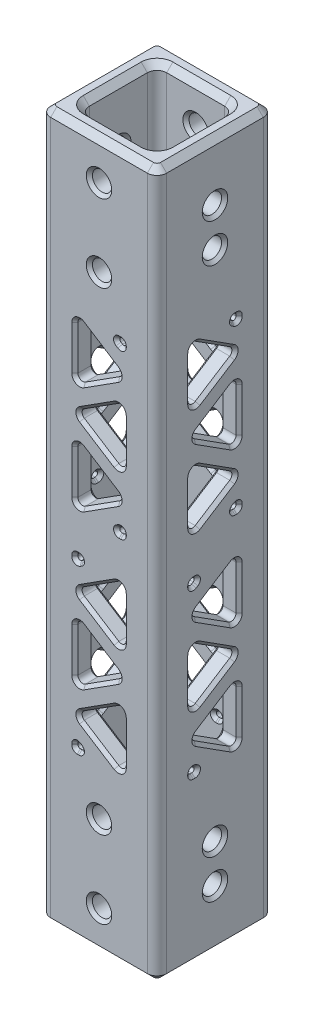
SolidWorks part; units mm, degrees
note: '?' marks a value the reader was unsure of.
ref_plane "Front Plane" through (0, 0, 0) normal (0, 0, 1) x (1, 0, 0)
ref_plane "Top Plane" through (0, 0, 0) normal (0, 1, 0) x (1, 0, 0)
ref_plane "Right Plane" through (0, 0, 0) normal (1, 0, 0) x (0, 0, -1)
sketch "Sketch1" plane through (0, 0, 0) normal (0, 1, 0) x (1, 0, 0)
  line L1 (-9.525, -9.525) -> (9.525, -9.525)
  line L2 (-9.525, -9.525) -> (-9.525, 9.525)
  line L3 (-9.525, 9.525) -> (9.525, 9.525)
  line L4 (9.525, -9.525) -> (9.525, 9.525)
  line L5 (-9.525, -9.525) -> (9.525, 9.525) construction
  line L6 (-9.525, 9.525) -> (9.525, -9.525) construction
  line L7 (-6.35, -6.35) -> (6.35, -6.35)
  line L8 (-6.35, -6.35) -> (-6.35, 6.35)
  line L9 (-6.35, 6.35) -> (6.35, 6.35)
  line L10 (6.35, -6.35) -> (6.35, 6.35)
  line L11 (-6.35, -6.35) -> (6.35, 6.35) construction
  line L12 (-6.35, 6.35) -> (6.35, -6.35) construction
  point P0 (0, 0)
  point P6 (0, 0)
  dimension "D1" = 19.05
  dimension "D2" = 19.05
  dimension "D3" = 12.7
extrude "Boss-Extrude1" add sketch "Sketch1" along normal mid plane 115.8875 contours L3 L4 L1 L2
hole_wizard "1/8 (0.125) Diameter Hole1" positions "Sketch15" profile "Sketch16" hole size "1/8" standard "ANSI Inch" end condition through all
sketch "Sketch15" plane through (0, 0, 9.525) normal (0, 0, -1) x (-1, 0, 0)
  line L0 (0, 38.8937) -> (0, 51.5937) construction
  line L4 (9.525, 57.9437) -> (-9.525, 57.9437) construction
  line L8 (0, 51.5937) -> (0, 57.9437) construction
  line L9 (0, -57.9437) -> (0, -51.5937) construction
  line L10 (-9.525, -57.9437) -> (9.525, -57.9437) construction
  line L11 (0, -51.5937) -> (0, -38.8937) construction
  point P0 (0, 51.5937)
  point P2 (0, 38.8937)
  point P4 (0, -38.8937)
  point P6 (0, -51.5937)
  dimension "D1" = 12.7
  dimension "D2" = 6.35
sketch "Sketch16" plane through (0, 51.5937, 9.525) normal (1, 0, 0) x (0, -1, 0)
  line L0 (0, 0) -> (0, 19.05)
  line L1 (0, 19.05) -> (1.5875, 19.05)
  line L2 (1.5875, 19.05) -> (1.5875, 0)
  line L5 (1.5875, 0) -> (0, 0)
  line L11 (0, -6.35) -> (0, 107.95) construction
  dimension "Thru Hole Dia." = 3.175
  dimension "Thru Hole Depth" = 19.05
hole_wizard "1/8 (0.125) Diameter Hole2" positions "Sketch8" profile "Sketch9" hole size "1/8" standard "ANSI Inch" end condition through all
sketch "Sketch8" plane through (-9.525, 0, 0) normal (-1, 0, 0) x (0, 0, 1)
  line L2 (0, 48.4187) -> (0, 57.9437) construction
  line L3 (-9.525, 57.9437) -> (9.525, 57.9437) construction
  point P0 (0, 48.4187)
  point P2 (0, 42.0687)
  dimension "D1" = 6.35
  dimension "D2" = 9.525
sketch "Sketch9" plane through (-9.525, 48.4187, 0) normal (0, 1, 0) x (0, 0, 1)
  line L0 (0, 0) -> (0, 19.05)
  line L1 (0, 19.05) -> (1.5875, 19.05)
  line L2 (1.5875, 19.05) -> (1.5875, 0)
  line L5 (1.5875, 0) -> (0, 0)
  line L11 (0, -6.35) -> (0, 107.95) construction
  dimension "Thru Hole Dia." = 3.175
  dimension "Thru Hole Depth" = 19.05
hole_wizard "1/8 (0.125) Diameter Hole3" positions "Sketch10" profile "Sketch11" hole size "1/8" standard "ANSI Inch" end condition through all
sketch "Sketch10" plane through (9.525, 0, 0) normal (1, 0, 0) x (0, 0, -1)
  line L0 (0, -57.9437) -> (0, -48.4187) construction
  line L1 (-9.525, -57.9437) -> (9.525, -57.9437) construction
  point P0 (0, -42.0687)
  point P2 (0, -48.4187)
  dimension "D1" = 6.35
  dimension "D2" = 9.525
sketch "Sketch11" plane through (9.525, -42.0687, 0) normal (0, 1, 0) x (0, 0, -1)
  line L0 (0, 0) -> (0, 19.05)
  line L1 (0, 19.05) -> (1.5875, 19.05)
  line L2 (1.5875, 19.05) -> (1.5875, 0)
  line L5 (1.5875, 0) -> (0, 0)
  line L11 (0, -6.35) -> (0, 107.95) construction
  dimension "Thru Hole Dia." = 3.175
  dimension "Thru Hole Depth" = 19.05
sketch "Sketch14" plane through (0, 0, 0) normal (0, 0, 1) x (1, 0, 0)
  line L0 (-3.9688, 30.9562) -> (3.9688, 30.9562) construction
  line L3 (3.9688, 30.9562) -> (3.9688, -30.9562) construction
  line L4 (3.9688, -30.9562) -> (-3.9688, -30.9562) construction
  line L5 (-3.9688, -30.9562) -> (-3.9688, 30.9562) construction
  line L6 (-3.9688, 30.9562) -> (-1.9357, 30.9562)
  line L7 (-1.9357, 30.9562) -> (-3.9688, 29.6596)
  line L8 (0, 30.9562) -> (0, 37.3062) construction
  line L11 (0, -37.3062) -> (0, -30.9562) construction
  line L12 (-3.9688, 3.175) -> (3.9688, 3.175) construction
  line L13 (-3.9688, -3.175) -> (3.9688, -3.175) construction
  line L14 (0, -3.175) -> (0, 3.175) construction
  line L15 (0, -30.9562) -> (0, -3.175) construction
  line L16 (0, 3.175) -> (0, 30.9562) construction
  line L17 (-3.9688, 29.6596) -> (-3.9688, 30.9562)
  line L18 (3.9688, 30.9562) -> (-3.9688, 25.8938)
  line L19 (-3.9688, 25.8938) -> (3.9688, 20.8314)
  line L20 (3.9688, 20.8314) -> (3.9688, 30.9562)
  line L21 (0, 28.425) -> (-1.7073, 31.1019) construction
  line L22 (-3.9688, 22.128) -> (3.9688, 17.0656)
  line L23 (3.9688, 17.0656) -> (-3.9688, 12.0032)
  line L24 (-3.9688, 12.0032) -> (-3.9688, 22.128)
  line L25 (0, 23.3626) -> (-1.7073, 20.6857) construction
  line L26 (3.9688, 13.2998) -> (-3.9688, 8.2374)
  line L27 (-3.9688, 8.2374) -> (3.9688, 3.175)
  line L28 (3.9688, 3.175) -> (3.9688, 13.2998)
  line L29 (0, 14.5344) -> (1.7073, 11.8575) construction
  line L30 (-1.9357, 3.175) -> (-3.9688, 3.175)
  line L31 (-3.9688, 3.175) -> (-3.9688, 4.4716)
  line L32 (-3.9688, 4.4716) -> (-1.9357, 3.175)
  line L33 (-2.9522, 3.8233) -> (-1.2449, 6.5002) construction
  line L34 (1.9357, -3.175) -> (3.9688, -3.175)
  line L35 (3.9688, -3.175) -> (3.9688, -4.4716)
  line L36 (3.9688, -4.4716) -> (1.9357, -3.175)
  line L37 (-3.9688, -3.175) -> (3.9688, -8.2374)
  line L38 (3.9688, -8.2374) -> (-3.9688, -13.2998)
  line L39 (-3.9688, -13.2998) -> (-3.9688, -3.175)
  line L40 (2.9522, -3.8233) -> (1.2449, -6.5002) construction
  line L41 (3.9688, -12.0032) -> (-3.9688, -17.0656)
  line L42 (-3.9688, -17.0656) -> (3.9688, -22.128)
  line L43 (3.9688, -22.128) -> (3.9688, -12.0032)
  line L44 (0, -14.5344) -> (-1.7073, -11.8575) construction
  line L45 (-3.9688, -30.9562) -> (3.9688, -25.8938)
  line L46 (3.9688, -25.8938) -> (-3.9688, -20.8314)
  line L47 (-3.9688, -20.8314) -> (-3.9688, -30.9562)
  line L48 (0, -23.3626) -> (1.7073, -20.6857) construction
  line L49 (1.9357, -30.9562) -> (3.9688, -30.9562)
  line L50 (3.9688, -30.9562) -> (3.9688, -29.6596)
  line L51 (3.9688, -29.6596) -> (1.9357, -30.9562)
  line L52 (2.9522, -30.3079) -> (1.2449, -27.631) construction
  line L54 (9.525, 57.9437) -> (9.525, -57.9437) construction
  circle A2 centre (0, -38.8937) radius 1.5875 construction
  circle A3 centre (0, 38.8937) radius 1.5875 construction
  dimension "D3" = 3.175
  dimension "D1" = 7.9375
  dimension "D2" = 6.35
extrude "Cut-Extrude1" cut sketch "Sketch14" against normal through all
ref_axis "Axis1" through (0, 63.7381, 0) along (0, -1, 0)?
pattern_circular "CirPattern2" count 4 over 360 about axis through (0, 0, 0) along (0, 1, 0) of "Cut-Extrude1"
fillet "Fillet1" radius 1.5875 8 edges at (9.525, 0, -9.525) (9.525, 0, 9.525) (-9.525, 0, -9.525) (-9.525, 0, 9.525) (6.35, 0, -6.35) (6.35, 0, 6.35) (-6.35, 0, 6.35) (-6.35, 0, -6.35)
fillet "Fillet2" radius 0.7937 72 edges at (3.9688, 30.9562, -7.9375) (3.9688, 20.8314, -7.9375) (-3.9687, 25.8938, -7.9375) (-3.9688, 12.0032, -7.9375) (-3.9688, 22.128, -7.9375) (3.9688, 17.0656, -7.9375) (-3.9688, -13.2998, -7.9375) (-3.9688, -3.175, -7.9375) (3.9688, -8.2374, -7.9375) (3.9688, 13.2998, -7.9375) (3.9688, 3.175, -7.9375) (-3.9687, 8.2374, -7.9375) (-3.9688, -30.9562, -7.9375) (-3.9688, -20.8314, -7.9375) (3.9688, -25.8938, -7.9375) (3.9688, -12.0032, -7.9375) (3.9688, -22.128, -7.9375) (-3.9688, -17.0656, -7.9375) (7.9375, -12.0032, 3.9688) (-7.9375, -13.2998, 3.9687) (7.9375, -13.2998, -3.9687) (7.9375, -30.9563, -3.9687) (-7.9375, -12.0032, -3.9688) (-7.9375, -30.9563, 3.9687) (7.9375, -22.128, 3.9688) (7.9375, -17.0656, -3.9687) (3.9688, -30.9562, 7.9375) (3.9688, -20.8314, 7.9375) (-3.9688, -25.8938, 7.9375) (3.9688, -13.2998, 7.9375) (3.9688, -3.175, 7.9375) (-3.9688, -8.2374, 7.9375) (7.9375, -20.8314, -3.9687) (7.9375, -25.8938, 3.9688) (7.9375, -3.175, -3.9687) (7.9375, -8.2374, 3.9688) (-3.9688, -12.0032, 7.9375) (-3.9688, -22.128, 7.9375) (3.9688, -17.0656, 7.9375) (-7.9375, -20.8314, 3.9687) (-7.9375, -25.8938, -3.9688) (-7.9375, -22.128, -3.9688) (-7.9375, -17.0656, 3.9687) (-7.9375, -3.175, 3.9687) (-7.9375, -8.2374, -3.9688) (7.9375, 12.0032, -3.9687) (-7.9375, 13.2998, -3.9688) (7.9375, 13.2998, 3.9688) (7.9375, 30.9562, 3.9688) (-7.9375, 30.9563, -3.9688) (-7.9375, 12.0032, 3.9687) (7.9375, 3.175, 3.9688) (7.9375, 8.2374, -3.9687) (-3.9688, 13.2998, 7.9375) (-3.9688, 3.175, 7.9375) (3.9687, 8.2374, 7.9375) (-3.9688, 30.9562, 7.9375) (-3.9688, 20.8314, 7.9375) (3.9688, 25.8938, 7.9375) (-7.9375, 20.8314, -3.9688) (-7.9375, 25.8938, 3.9687) (-7.9375, 22.128, 3.9687) (-7.9375, 17.0656, -3.9688) (3.9688, 12.0032, 7.9375) (3.9688, 22.128, 7.9375) (-3.9688, 17.0656, 7.9375) (7.9375, 20.8314, 3.9688) (7.9375, 25.8938, -3.9687) (7.9375, 22.128, -3.9687) (7.9375, 17.0656, 3.9688) (-7.9375, 3.175, -3.9688) (-7.9375, 8.2374, 3.9687)
fillet "Fillet3" radius 0.3969 48 edges at (3.9688, -3.175, -7.9375) (3.9688, -4.4716, -7.9375) (1.9357, -3.175, -7.9375) (-3.9688, 3.175, -7.9375) (-3.9688, 4.4716, -7.9375) (-1.9357, 3.175, -7.9375) (3.9688, -29.6596, -7.9375) (3.9688, -30.9562, -7.9375) (1.9357, -30.9563, -7.9375) (-3.9687, 29.6596, -7.9375) (-3.9688, 30.9562, -7.9375) (-1.9357, 30.9562, -7.9375) (-7.9375, -29.6596, -3.9688) (7.9375, -29.6596, 3.9688) (7.9375, -30.9562, 1.9357) (7.9375, -30.9562, 3.9688) (-7.9375, -3.175, -3.9688) (7.9375, -3.175, 3.9688) (7.9375, -4.4716, 3.9688) (7.9375, -3.175, 1.9357) (-7.9375, -4.4716, -3.9688) (-7.9375, -3.175, -1.9357) (-7.9375, -30.9562, -3.9688) (-7.9375, -30.9563, -1.9357) (-3.9688, -3.175, 7.9375) (-3.9688, -4.4716, 7.9375) (-1.9357, -3.175, 7.9375) (-3.9688, -29.6596, 7.9375) (-1.9357, -30.9562, 7.9375) (-3.9688, -30.9562, 7.9375) (7.9375, 29.6596, -3.9687) (7.9375, 3.175, -3.9687) (7.9375, 30.9562, -3.9687) (7.9375, 30.9562, -1.9357) (3.9688, 3.175, 7.9375) (3.9688, 4.4716, 7.9375) (1.9357, 3.175, 7.9375) (-7.9375, 29.6596, 3.9687) (-7.9375, 30.9562, 3.9687) (-7.9375, 30.9562, 1.9357) (3.9688, 29.6596, 7.9375) (3.9688, 30.9562, 7.9375) (1.9357, 30.9562, 7.9375) (-7.9375, 3.175, 3.9687) (-7.9375, 4.4716, 3.9687) (-7.9375, 3.175, 1.9357) (7.9375, 4.4716, -3.9687) (7.9375, 3.175, -1.9357)
chamfer "Chamfer1" distance 1.016 angle 45 32 edges at (9.525, 57.9437, 0) (9.06, 57.9437, -9.06) (9.06, 57.9437, 9.06) (0, 57.9437, -9.525) (0, 57.9437, 9.525) (-9.06, 57.9437, -9.06) (-9.06, 57.9437, 9.06) (-9.525, 57.9437, 0) (6.35, 57.9437, 0) (5.885, 57.9437, -5.885) (5.885, 57.9437, 5.885) (0, 57.9437, -6.35) (0, 57.9437, 6.35) (-5.885, 57.9437, -5.885) (-5.885, 57.9437, 5.885) (-6.35, 57.9437, 0) (0, -57.9437, 9.525) (9.06, -57.9437, 9.06) (-9.06, -57.9437, 9.06) (9.525, -57.9437, 0) (-9.525, -57.9437, 0) (9.06, -57.9437, -9.06) (-9.06, -57.9437, -9.06) (0, -57.9437, -9.525) (0, -57.9437, 6.35) (5.885, -57.9437, 5.885) (-5.885, -57.9437, 5.885) (6.35, -57.9437, 0) (-6.35, -57.9437, 0) (5.885, -57.9437, -5.885) (-5.885, -57.9437, -5.885) (0, -57.9437, -6.35)
chamfer "Chamfer2" distance 0.508 angle 45 512 edges at (9.525, -12.5482, -3.5566) (6.35, 21.3764, -3.5566) (9.525, 21.3764, -3.5566) (6.35, 17.0656, 3.2864) (9.525, 17.0656, 3.2864) (6.35, 12.7549, -3.5566) (9.525, 12.7549, -3.5566) (6.35, 21.5831, 3.5566) (9.525, 21.5831, 3.5566) (6.35, 30.2046, 3.5566) (9.525, 30.2046, 3.5566) (6.35, 25.8938, -3.2864) (9.525, 25.8938, -3.2864) (3.5566, -21.3764, -6.35) (3.5566, -21.3764, -9.525) (-3.2864, -17.0656, -6.35) (-3.2864, -17.0656, -9.525) (3.5566, -12.7549, -6.35) (3.5566, -12.7549, -9.525) (-3.5566, -21.5831, -6.35) (-3.5566, -21.5831, -9.525) (3.2864, -25.8938, -6.35) (3.2864, -25.8938, -9.525) (-3.5566, -30.2046, -6.35) (-3.5566, -30.2046, -9.525) (3.5566, 3.9267, -6.35) (3.5566, 3.9267, -9.525) (-3.2864, 8.2374, -6.35) (-3.2864, 8.2374, -9.525) (3.5566, 12.5482, -6.35) (3.5566, 12.5482, -9.525) (-3.5566, -3.9267, -6.35) (-3.5566, -3.9267, -9.525) (3.2864, -8.2374, -6.35) (3.2864, -8.2374, -9.525) (-3.5566, -12.5482, -6.35) (-3.5566, -12.5482, -9.525) (-3.5566, 21.3764, -6.35) (-3.5566, 21.3764, -9.525) (3.2864, 17.0656, -6.35) (3.2864, 17.0656, -9.525) (-3.5566, 12.7549, -6.35) (-3.5566, 12.7549, -9.525) (3.5566, 21.5831, -6.35) (3.5566, 21.5831, -9.525) (3.5566, 30.2046, -6.35) (3.5566, 30.2046, -9.525) (-3.2864, 25.8938, -6.35) (-3.2864, 25.8938, -9.525) (-3.434, -30.9562, 6.35) (-3.434, -30.9562, 9.525) (-3.2206, -30.1368, 6.35) (-3.2206, -30.1368, 9.525) (-3.9688, -30.4714, 6.35) (-3.9688, -30.4714, 9.525) (-3.2206, -3.9944, 6.35) (-3.2206, -3.9944, 9.525) (-3.434, -3.175, 6.35) (-3.434, -3.175, 9.525) (-3.9688, -3.6598, 6.35) (-3.9688, -3.6598, 9.525) (3.2206, 3.9944, 6.35) (3.2206, 3.9944, 9.525) (3.434, 3.175, 6.35) (3.434, 3.175, 9.525) (3.9688, 3.6598, 6.35) (3.9688, 3.6598, 9.525) (3.2206, 30.1368, 6.35) (3.2206, 30.1368, 9.525) (3.9688, 30.4714, 6.35) (3.9688, 30.4714, 9.525) (3.434, 30.9562, 6.35) (3.434, 30.9562, 9.525) (-6.35, -30.9562, -3.434) (-9.525, -30.9562, -3.434) (-6.35, -30.1368, -3.2206) (-9.525, -30.1368, -3.2206) (-6.35, -30.4714, -3.9688) (-9.525, -30.4714, -3.9688) (-6.35, -3.9944, -3.2206) (-9.525, -3.9944, -3.2206) (-6.35, -3.175, -3.434) (-9.525, -3.175, -3.434) (-6.35, -3.6598, -3.9688) (-9.525, -3.6598, -3.9688) (-6.35, 3.175, 3.434) (-9.525, 3.175, 3.434) (-6.35, 3.6598, 3.9687) (-9.525, 3.6598, 3.9687) (-6.35, 3.9944, 3.2206) (-9.525, 3.9944, 3.2206) (-6.35, 30.9562, 3.434) (-9.525, 30.9562, 3.434) (-6.35, 30.1368, 3.2206) (-9.525, 30.1368, 3.2206) (-6.35, 30.4714, 3.9687) (-9.525, 30.4714, 3.9687) (6.35, 30.9562, -3.434) (9.525, 30.9562, -3.434) (6.35, 30.1368, -3.2206) (9.525, 30.1368, -3.2206) (6.35, 30.4714, -3.9687) (9.525, 30.4714, -3.9687) (6.35, -30.4714, 3.9688) (9.525, -30.4714, 3.9688) (6.35, -30.9562, 3.434) (9.525, -30.9562, 3.434) (6.35, -30.1368, 3.2206) (9.525, -30.1368, 3.2206) (6.35, 3.6598, -3.9687) (9.525, 3.6598, -3.9687) (6.35, 3.9944, -3.2206) (9.525, 3.9944, -3.2206) (6.35, 3.175, -3.434) (9.525, 3.175, -3.434) (6.35, -3.6598, 3.9688) (9.525, -3.6598, 3.9688) (6.35, -3.9944, 3.2206) (9.525, -3.9944, 3.2206) (6.35, -3.175, 3.434) (9.525, -3.175, 3.434) (-3.434, 30.9562, -6.35) (-3.434, 30.9562, -9.525) (-3.2206, 30.1368, -6.35) (-3.2206, 30.1368, -9.525) (-3.9688, 30.4714, -6.35) (-3.9688, 30.4714, -9.525) (3.9688, -30.4714, -6.35) (3.9688, -30.4714, -9.525) (3.434, -30.9562, -6.35) (3.434, -30.9562, -9.525) (3.2206, -30.1368, -6.35) (3.2206, -30.1368, -9.525) (-3.9688, 3.6598, -6.35) (-3.9688, 3.6598, -9.525) (-3.2206, 3.9944, -6.35) (-3.2206, 3.9944, -9.525) (-3.434, 3.175, -6.35) (-3.434, 3.175, -9.525) (3.9688, -3.6598, -6.35) (3.9688, -3.6598, -9.525) (3.2206, -3.9944, -6.35) (3.2206, -3.9944, -9.525) (3.434, -3.175, -6.35) (3.434, -3.175, -9.525) (-2.9151, -30.6705, 6.35) (-2.9151, -30.6705, 9.525) (-3.7627, -30.0355, 6.35) (-3.7627, -30.0355, 9.525) (-3.8525, -30.84, 6.35) (-3.8525, -30.84, 9.525) (-2.9151, -3.4607, 6.35) (-2.9151, -3.4607, 9.525) (-3.7627, -4.0958, 6.35) (-3.7627, -4.0958, 9.525) (-3.8525, -3.2912, 6.35) (-3.8525, -3.2912, 9.525) (2.9151, 3.4607, 6.35) (2.9151, 3.4607, 9.525) (3.7627, 4.0958, 6.35) (3.7627, 4.0958, 9.525) (3.8525, 3.2912, 6.35) (3.8525, 3.2912, 9.525) (3.7627, 30.0355, 6.35) (3.7627, 30.0355, 9.525) (3.8525, 30.84, 6.35) (3.8525, 30.84, 9.525) (2.9151, 30.6705, 6.35) (2.9151, 30.6705, 9.525) (-6.35, -30.6705, -2.9151) (-9.525, -30.6705, -2.9151) (-6.35, -30.0355, -3.7627) (-9.525, -30.0355, -3.7627) (-6.35, -30.84, -3.8525) (-9.525, -30.84, -3.8525) (-6.35, -3.4607, -2.9151) (-9.525, -3.4607, -2.9151) (-6.35, -4.0958, -3.7627) (-9.525, -4.0958, -3.7627) (-6.35, -3.2912, -3.8525) (-9.525, -3.2912, -3.8525) (-6.35, 3.2912, 3.8525) (-9.525, 3.2912, 3.8525) (-6.35, 4.0958, 3.7627) (-9.525, 4.0958, 3.7627) (-6.35, 3.4607, 2.9151) (-9.525, 3.4607, 2.9151) (-6.35, 30.6705, 2.9151) (-9.525, 30.6705, 2.9151) (-6.35, 30.0355, 3.7627) (-9.525, 30.0355, 3.7627) (-6.35, 30.84, 3.8525) (-9.525, 30.84, 3.8525) (6.35, 30.6705, -2.9151) (9.525, 30.6705, -2.9151) (6.35, 30.0355, -3.7627) (9.525, 30.0355, -3.7627) (6.35, -30.84, 3.8525) (9.525, -30.84, 3.8525) (6.35, -30.6705, 2.9151) (9.525, -30.6705, 2.9151) (6.35, -30.0355, 3.7627) (9.525, -30.0355, 3.7627) (6.35, 4.0958, -3.7627) (9.525, 4.0958, -3.7627) (6.35, 3.4607, -2.9151) (9.525, 3.4607, -2.9151) (6.35, 3.2912, -3.8525) (9.525, 3.2912, -3.8525) (6.35, -4.0958, 3.7627) (9.525, -4.0958, 3.7627) (6.35, -3.4607, 2.9151) (9.525, -3.4607, 2.9151) (6.35, -3.2912, 3.8525) (9.525, -3.2912, 3.8525) (6.35, 30.84, -3.8525) (9.525, 30.84, -3.8525) (-2.9151, 30.6705, -6.35) (-2.9151, 30.6705, -9.525) (-3.7627, 30.0355, -6.35) (-3.7627, 30.0355, -9.525) (3.8525, -30.84, -6.35) (3.8525, -30.84, -9.525) (2.9151, -30.6705, -6.35) (2.9151, -30.6705, -9.525) (3.7627, -30.0355, -6.35) (3.7627, -30.0355, -9.525) (-3.7627, 4.0958, -6.35) (-3.7627, 4.0958, -9.525) (-2.9151, 3.4607, -6.35) (-2.9151, 3.4607, -9.525) (-3.8525, 3.2912, -6.35) (-3.8525, 3.2912, -9.525) (3.7627, -4.0958, -6.35) (3.7627, -4.0958, -9.525) (2.9151, -3.4607, -6.35) (2.9151, -3.4607, -9.525) (3.8525, -3.2912, -6.35) (3.8525, -3.2912, -9.525) (-3.8525, 30.84, -6.35) (-3.8525, 30.84, -9.525) (1.5875, -51.5937, -6.35) (-1.5875, -51.5937, 6.35) (1.5875, -51.5937, 9.525) (1.5875, -51.5937, -9.525) (1.5875, -38.8937, -6.35) (-1.5875, -38.8937, 6.35) (1.5875, -38.8937, 9.525) (1.5875, -38.8937, -9.525) (1.5875, 38.8937, -6.35) (-1.5875, 38.8937, 6.35) (1.5875, 38.8937, 9.525) (1.5875, 38.8937, -9.525) (1.5875, 51.5937, -6.35) (-1.5875, 51.5937, 6.35) (1.5875, 51.5937, 9.525) (1.5875, 51.5937, -9.525) (6.35, 42.0687, 1.5875) (-6.35, 42.0687, -1.5875) (-9.525, 42.0687, 1.5875) (9.525, 42.0687, 1.5875) (6.35, 48.4187, 1.5875) (-6.35, 48.4187, -1.5875) (-9.525, 48.4187, 1.5875) (9.525, 48.4187, 1.5875) (-6.35, -23.4172, -0.0856) (-9.525, -23.4172, -0.0856) (-6.35, -28.3704, -0.0856) (-9.525, -28.3704, -0.0856) (-6.35, -25.8938, 3.9687) (-9.525, -25.8938, 3.9687) (-6.35, -14.589, 0.0856) (-9.525, -14.589, 0.0856) (-6.35, -17.0656, -3.9688) (-9.525, -17.0656, -3.9688) (-6.35, -19.5422, 0.0856) (-9.525, -19.5422, 0.0856) (-6.35, -10.714, -0.0856) (-9.525, -10.714, -0.0856) (-6.35, -8.2374, 3.9687) (-9.525, -8.2374, 3.9687) (-6.35, -5.7608, -0.0856) (-9.525, -5.7608, -0.0856) (-6.35, 10.714, 0.0856) (-9.525, 10.714, 0.0856) (-6.35, 8.2374, -3.9688) (-9.525, 8.2374, -3.9688) (-6.35, 5.7608, 0.0856) (-9.525, 5.7608, 0.0856) (-6.35, 14.589, -0.0856) (-9.525, 14.589, -0.0856) (-6.35, 17.0656, 3.9687) (-9.525, 17.0656, 3.9687) (-6.35, 19.5422, -0.0856) (-9.525, 19.5422, -0.0856) (-6.35, 28.3704, 0.0856) (-9.525, 28.3704, 0.0856) (-6.35, 25.8938, -3.9688) (-9.525, 25.8938, -3.9688) (-6.35, 23.4172, 0.0856) (-9.525, 23.4172, 0.0856) (-0.0856, -28.3704, 6.35) (-0.0856, -28.3704, 9.525) (3.9688, -25.8938, 6.35) (3.9688, -25.8938, 9.525) (-0.0856, -23.4172, 6.35) (-0.0856, -23.4172, 9.525) (0.0856, -14.589, 6.35) (0.0856, -14.589, 9.525) (-3.9688, -17.0656, 6.35) (-3.9688, -17.0656, 9.525) (0.0856, -19.5422, 6.35) (0.0856, -19.5422, 9.525) (-0.0856, -10.714, 6.35) (-0.0856, -10.714, 9.525) (3.9688, -8.2374, 6.35) (3.9688, -8.2374, 9.525) (-0.0856, -5.7608, 6.35) (-0.0856, -5.7608, 9.525) (0.0856, 10.714, 6.35) (0.0856, 10.714, 9.525) (-3.9688, 8.2374, 6.35) (-3.9688, 8.2374, 9.525) (0.0856, 5.7608, 6.35) (0.0856, 5.7608, 9.525) (-0.0856, 19.5422, 6.35) (-0.0856, 19.5422, 9.525) (-0.0856, 14.589, 6.35) (-0.0856, 14.589, 9.525) (3.9688, 17.0656, 6.35) (3.9688, 17.0656, 9.525) (0.0856, 23.4172, 6.35) (0.0856, 23.4172, 9.525) (0.0856, 28.3704, 6.35) (0.0856, 28.3704, 9.525) (-3.9688, 25.8938, 6.35) (-3.9688, 25.8938, 9.525) (6.35, -17.0656, 3.9688) (9.525, -17.0656, 3.9688) (6.35, -19.5422, -0.0856) (9.525, -19.5422, -0.0856) (6.35, -14.589, -0.0856) (9.525, -14.589, -0.0856) (6.35, -25.8938, -3.9687) (9.525, -25.8938, -3.9687) (6.35, -23.4172, 0.0856) (9.525, -23.4172, 0.0856) (6.35, -28.3704, 0.0856) (9.525, -28.3704, 0.0856) (6.35, 8.2374, 3.9688) (9.525, 8.2374, 3.9688) (6.35, 5.7608, -0.0856) (9.525, 5.7608, -0.0856) (6.35, 10.714, -0.0856) (9.525, 10.714, -0.0856) (6.35, -48.4187, 1.5875) (-6.35, -48.4187, -1.5875) (6.35, -8.2374, -3.9687) (9.525, -8.2374, -3.9687) (-9.525, -48.4187, -1.5875) (9.525, -48.4187, -1.5875) (6.35, -5.7608, 0.0856) (9.525, -5.7608, 0.0856) (6.35, -10.714, 0.0856) (9.525, -10.714, 0.0856) (6.35, 17.0656, -3.9687) (9.525, 17.0656, -3.9687) (6.35, 19.5422, 0.0856) (9.525, 19.5422, 0.0856) (6.35, 14.589, 0.0856) (9.525, 14.589, 0.0856) (6.35, 25.8938, 3.9688) (9.525, 25.8938, 3.9688) (6.35, 23.4172, -0.0856) (9.525, 23.4172, -0.0856) (6.35, 28.3704, -0.0856) (9.525, 28.3704, -0.0856) (3.9688, -17.0656, -6.35) (3.9688, -17.0656, -9.525) (-0.0856, -19.5422, -6.35) (-0.0856, -19.5422, -9.525) (-0.0856, -14.589, -6.35) (-0.0856, -14.589, -9.525) (-3.9688, -25.8938, -6.35) (-3.9688, -25.8938, -9.525) (0.0856, -23.4172, -6.35) (0.0856, -23.4172, -9.525) (0.0856, -28.3704, -6.35) (0.0856, -28.3704, -9.525) (3.9688, 8.2374, -6.35) (3.9688, 8.2374, -9.525) (-0.0856, 5.7608, -6.35) (-0.0856, 5.7608, -9.525) (-0.0856, 10.714, -6.35) (-0.0856, 10.714, -9.525) (-3.9688, -8.2374, -6.35) (-3.9688, -8.2374, -9.525) (0.0856, -5.7608, -6.35) (0.0856, -5.7608, -9.525) (0.0856, -10.714, -6.35) (0.0856, -10.714, -9.525) (-3.9688, 17.0656, -6.35) (-3.9688, 17.0656, -9.525) (0.0856, 19.5422, -6.35) (0.0856, 19.5422, -9.525) (0.0856, 14.589, -6.35) (0.0856, 14.589, -9.525) (3.9688, 25.8938, -6.35) (3.9688, 25.8938, -9.525) (-0.0856, 23.4172, -6.35) (-0.0856, 23.4172, -9.525) (-0.0856, 28.3704, -6.35) (-0.0856, 28.3704, -9.525) (-6.35, -25.8938, -3.2864) (-9.525, -25.8938, -3.2864) (-6.35, -21.5831, 3.5566) (-9.525, -21.5831, 3.5566) (-6.35, -30.2046, 3.5566) (-9.525, -30.2046, 3.5566) (-6.35, -12.7549, -3.5566) (-9.525, -12.7549, -3.5566) (-6.35, -21.3764, -3.5566) (-9.525, -21.3764, -3.5566) (-6.35, -17.0656, 3.2864) (-9.525, -17.0656, 3.2864) (-6.35, -12.5482, 3.5566) (-9.525, -12.5482, 3.5566) (-6.35, -3.9267, 3.5566) (-9.525, -3.9267, 3.5566) (-6.35, -8.2374, -3.2864) (-9.525, -8.2374, -3.2864) (-6.35, 12.5482, -3.5566) (-9.525, 12.5482, -3.5566) (-6.35, 3.9267, -3.5566) (-9.525, 3.9267, -3.5566) (-6.35, 8.2374, 3.2864) (-9.525, 8.2374, 3.2864) (-6.35, 12.7549, 3.5566) (-9.525, 12.7549, 3.5566) (-6.35, 21.3764, 3.5566) (-9.525, 21.3764, 3.5566) (-6.35, 17.0656, -3.2864) (-9.525, 17.0656, -3.2864) (-6.35, 30.2046, -3.5566) (-9.525, 30.2046, -3.5566) (-6.35, 21.5831, -3.5566) (-9.525, 21.5831, -3.5566) (-6.35, 25.8938, 3.2864) (-9.525, 25.8938, 3.2864) (3.5566, -30.2046, 6.35) (3.5566, -30.2046, 9.525) (6.35, -42.0687, 1.5875) (3.5566, -21.5831, 6.35) (3.5566, -21.5831, 9.525) (-6.35, -42.0687, -1.5875) (-3.2864, -25.8938, 6.35) (-3.2864, -25.8938, 9.525) (-3.5566, -12.7549, 6.35) (-9.525, -42.0687, -1.5875) (-3.5566, -12.7549, 9.525) (-3.5566, -21.3764, 6.35) (9.525, -42.0687, -1.5875) (-3.5566, -21.3764, 9.525) (3.2864, -17.0656, 6.35) (3.2864, -17.0656, 9.525) (3.5566, -12.5482, 6.35) (3.5566, -12.5482, 9.525) (3.5566, -3.9267, 6.35) (3.5566, -3.9267, 9.525) (-3.2864, -8.2374, 6.35) (-3.2864, -8.2374, 9.525) (-3.5566, 12.5482, 6.35) (-3.5566, 12.5482, 9.525) (-3.5566, 3.9267, 6.35) (-3.5566, 3.9267, 9.525) (3.2864, 8.2374, 6.35) (3.2864, 8.2374, 9.525) (-3.2864, 17.0656, 6.35) (-3.2864, 17.0656, 9.525) (3.5566, 12.7549, 6.35) (3.5566, 12.7549, 9.525) (3.5566, 21.3764, 6.35) (3.5566, 21.3764, 9.525) (3.2864, 25.8938, 6.35) (3.2864, 25.8938, 9.525) (-3.5566, 30.2046, 6.35) (-3.5566, 30.2046, 9.525) (-3.5566, 21.5831, 6.35) (-3.5566, 21.5831, 9.525) (6.35, -21.3764, 3.5566) (9.525, -21.3764, 3.5566) (6.35, -17.0656, -3.2864) (9.525, -17.0656, -3.2864) (6.35, -12.7549, 3.5566) (9.525, -12.7549, 3.5566) (6.35, -21.5831, -3.5566) (9.525, -21.5831, -3.5566) (6.35, -25.8938, 3.2864) (9.525, -25.8938, 3.2864) (6.35, -30.2046, -3.5566) (9.525, -30.2046, -3.5566) (6.35, 3.9267, 3.5566) (9.525, 3.9267, 3.5566) (6.35, 8.2374, -3.2864) (9.525, 8.2374, -3.2864) (6.35, 12.5482, 3.5566) (9.525, 12.5482, 3.5566) (6.35, -3.9267, -3.5566) (9.525, -3.9267, -3.5566) (6.35, -8.2374, 3.2864) (9.525, -8.2374, 3.2864) (6.35, -12.5482, -3.5566)
equation "\"D2@Sketch1\"=\"D1@Sketch1\""
